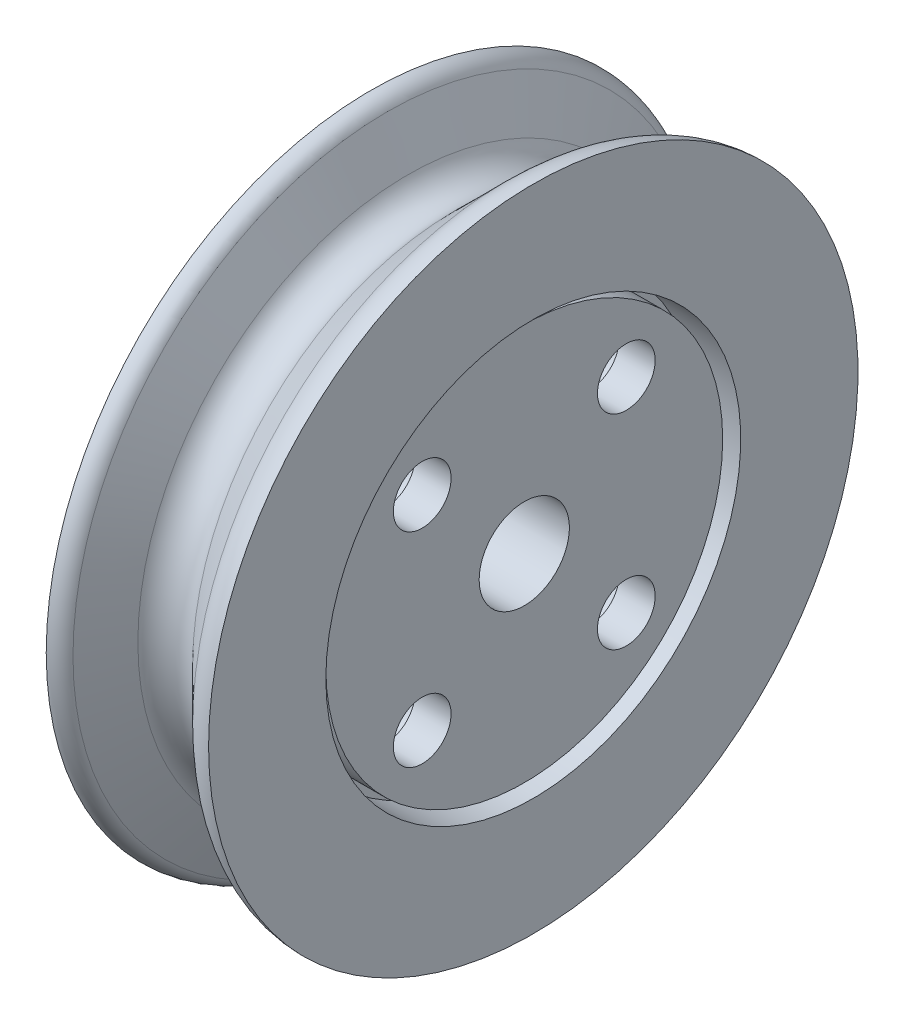
SolidWorks part; units mm, degrees
ref_plane "Front Plane" through (0, 0, 0) normal (0, 0, 1) x (1, 0, 0)
ref_plane "Top Plane" through (0, 0, 0) normal (0, 1, 0) x (1, 0, 0)
ref_plane "Right Plane" through (0, 0, 0) normal (1, 0, 0) x (0, 0, -1)
sketch "Sketch1" plane through (0, 0, 0) normal (0, 1, 0) x (1, 0, 0)
  line L0 (0, 5) -> (10, 5)
  line L1 (10, 5) -> (10, 11)
  line L2 (10, 11) -> (12, 11)
  line L3 (12, 11) -> (12, 2.5)
  line L4 (12, 2.5) -> (0, 2.5)
  line L5 (0, 2.5) -> (0, 5)
  line L6 (0, 0) -> (30.6885, 0) construction
  dimension "D1" = 2.5
  dimension "D2" = 5
  dimension "D3" = 12
  dimension "D4" = 11
  dimension "D5" = 2
revolve "Revolve1" add sketch "Sketch1" angle 360 about L6
sketch "Sketch2" plane through (12, 0, 0) normal (1, 0, 0) x (0, 0, -1)
  line L1 (5.6569, -5.6569) -> (-5.6569, -5.6569) construction
  line L2 (5.6569, -5.6569) -> (5.6569, 5.6569) construction
  line L3 (5.6569, 5.6569) -> (-5.6569, 5.6569) construction
  line L4 (-5.6569, -5.6569) -> (-5.6569, 5.6569) construction
  line L5 (5.6569, -5.6569) -> (-5.6569, 5.6569) construction
  line L6 (5.6569, 5.6569) -> (-5.6569, -5.6569) construction
  circle A0 centre (-5.6569, 5.6569) radius 1.6
  circle A1 centre (-5.6569, -5.6569) radius 1.6
  circle A2 centre (5.6569, -5.6569) radius 1.6
  circle A3 centre (5.6569, 5.6569) radius 1.6
  point P0 (0, 0)
  dimension "D2" = 3.2
  dimension "D1" = 16
extrude "Cut-Extrude1" cut sketch "Sketch2" against normal through all
sketch "Sketch3" plane through (0, 0, 0) normal (0, 1, 0) x (1, 0, 0)
  line L0 (10, 5) -> (10, 11.5)
  line L1 (10, 11.5) -> (12.5, 11.5)
  line L2 (12.5, 11.5) -> (12.5, 18)
  line L3 (10.9916, 17.3752) -> (8.1314, 14.515)
  line L4 (5.5499, 14.9702) -> (4.4063, 17.4226)
  line L5 (3.5, 18) -> (3.5, 5.5)
  line L6 (3.5, 5.5) -> (4, 5)
  line L7 (10, 5) -> (0, 5) construction
  line L8 (4, 5) -> (10, 5)
  line L9 (12, 11) -> (10, 11) construction
  line L10 (0, 0) -> (15.2036, 0) construction
  arc A0 (12.5, 18) -> (10.9916, 17.3752) centre (12.5, 15.8668) ccw
  arc A1 (8.1314, 14.515) -> (5.5499, 14.9702) centre (7, 15.6463) cw
  arc A2 (4.4063, 17.4226) -> (3.5, 18) centre (3.5, 17) ccw
  dimension "D1" = 0.5
  dimension "D4" = 1.6
  dimension "D9" = 1
  dimension "D2" = 6
  dimension "D3" = 45
  dimension "D5" = 2.5
  dimension "D6" = 45
  dimension "D7" = 25
  dimension "D8" = 18
  dimension "D10" = 9
  dimension "D11" = 5.5
revolve "Revolve2" add sketch "Sketch3" angle 360 about L10
sketch "Sketch4" plane through (0, 0, 0) normal (0, 0, 1) x (1, 0, 0)
  line L0 (3.5, 18) -> (3.5, -18) construction
  line L3 (7, 0) -> (3.5, 0)
  line L5 (3.5, 0) -> (3.5, 14)
  line L6 (3.5, 14) -> (1.5355, 18.2128) construction
  line L7 (5.5499, 14.9702) -> (4.4063, 17.4226) construction
  arc A0 (3.5, 14) -> (7, 0) centre (-30.8839, -2.0335) cw
  point P6 (6.6878, 5)
  point P7 (0, 0)
  point P8 (7, 2.7058)
  point P9 (3.5, 0)
  point P12 (3.5, 14.8085)
  dimension "D1" = 14
  dimension "D2" = 3.5
extrude "Cut-Extrude3" cut sketch "Sketch4" against normal mid plane 6
mirror "Mirror1" about plane through (0, 0, 0) normal (0, 1, 0) of "Cut-Extrude3"
sketch "Sketch5" plane through (10, 0, 0) normal (1, 0, 0) x (0, 0, -1)
  circle A0 centre (-5.6569, 5.6569) radius 1.8
  circle A1 centre (5.6569, 5.6569) radius 1.8
  circle A2 centre (5.6569, -5.6569) radius 1.8
  circle A3 centre (-5.6569, -5.6569) radius 1.8
  circle A4 centre (-5.6569, -5.6569) radius 1.6 construction
  point P11 (0, 0)
  point P12 (0, 0)
  point P15 (0, 0)
  dimension "D1" = 3.6
extrude "Cut-Extrude4" cut sketch "Sketch5" against normal through all
